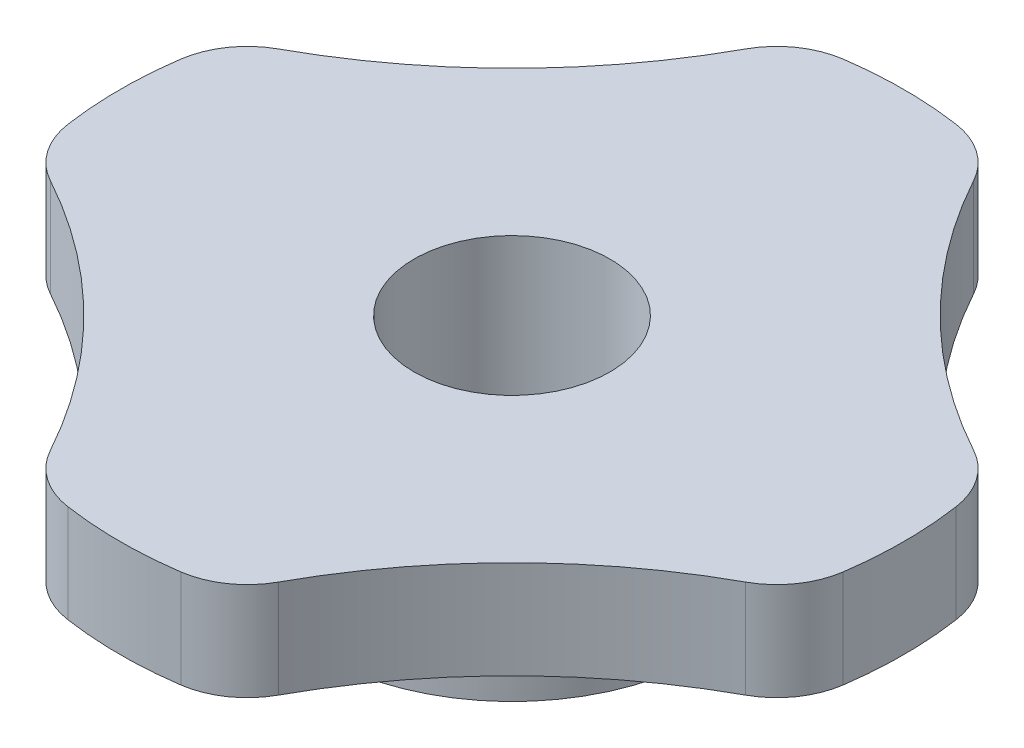
SolidWorks part; units mm, degrees
ref_plane "Front Plane" through (0, 0, 0) normal (0, 0, 1) x (1, 0, 0)
ref_plane "Top Plane" through (0, 0, 0) normal (0, 1, 0) x (1, 0, 0)
ref_plane "Right Plane" through (0, 0, 0) normal (1, 0, 0) x (0, 0, -1)
sketch "Sketch1" plane through (0, 0, 0) normal (0, 1, 0) x (1, 0, 0)
  line L0 (-3.175, 12.2967) -> (-3.175, 5.4993)
  line L1 (3.175, 12.2967) -> (3.175, 5.4993)
  line L2 (0, 0) -> (0, 12.7) construction
  line L3 (12.2967, 3.175) -> (5.4993, 3.175)
  line L4 (12.2967, -3.175) -> (5.4993, -3.175)
  line L5 (3.175, -12.2967) -> (3.175, -5.4993)
  line L6 (-3.175, -12.2967) -> (-3.175, -5.4993)
  line L7 (-12.2967, -3.175) -> (-5.4993, -3.175)
  line L8 (-12.2967, 3.175) -> (-5.4993, 3.175)
  circle A0 centre (0, 0) radius 6.35
  circle A1 centre (0, 0) radius 3.175
  circle A2 centre (0, 0) radius 12.7
  arc A3 (-3.175, 12.2967) -> (-12.2967, 3.175) centre (-20.4106, 20.4106) cw
  arc A4 (12.2967, 3.175) -> (3.175, 12.2967) centre (20.4106, 20.4106) cw
  arc A5 (3.175, -12.2967) -> (12.2967, -3.175) centre (20.4106, -20.4106) cw
  arc A6 (-12.2967, -3.175) -> (-3.175, -12.2967) centre (-20.4106, -20.4106) cw
  point P25 (0, 0)
  point P36 (0, 0)
  dimension "D1" = 12.7
  dimension "D2" = 6.35
  dimension "D3" = 25.4
  dimension "D7" = 19.05
  dimension "D4" = 6.35
  dimension "D5" = 3.175
  dimension "D6" = 4
  dimension "D8" = 4
extrude "Boss-Extrude1" add sketch "Sketch1" along normal blind 3.175 contours L8 A2 L7 A0 | A0 L2 A2 L0 | L2 A0 L1 A2 | A1 A0 | L4 A2 L3 A0 | L6 A2 L5 A0 | L5 A2 L4 A0 | L3 A2 L1 A0 | L7 A2 L6 A0 | L0 A2 L8 A0 region at (-1.6053, 0, -9.3167) region at (-6.0514, 0, -6.0514) region at (-1.597, 0, -5.9601) region at (1.6053, 0, -9.3167) region at (-9.3167, 0, 0) region at (6.0514, 0, -6.0514) region at (-6.0514, 0, 6.0514) region at (9.3167, 0, 0) region at (0, 0, 9.3167) region at (6.0514, 0, 6.0514)
extrude "Boss-Extrude2" add sketch "Sketch1<3>" against normal blind 3.175 contours A1 A0 region at (0, 0, -6.1704)
sketch "Sketch1<3>" plane through (0, 0, 0) normal (0, 1, 0) x (1, 0, 0) same geometry as "Sketch1"
fillet "Fillet1" radius 2.54 8 edges at (12.2967, 1.5875, -3.175) (12.2967, 1.5875, 3.175) (3.175, 1.5875, 12.2967) (-3.175, 1.5875, 12.2967) (-12.2967, 1.5875, 3.175) (-12.2967, 1.5875, -3.175) (3.175, 1.5875, -12.2967) (-3.175, 1.5875, -12.2967)
